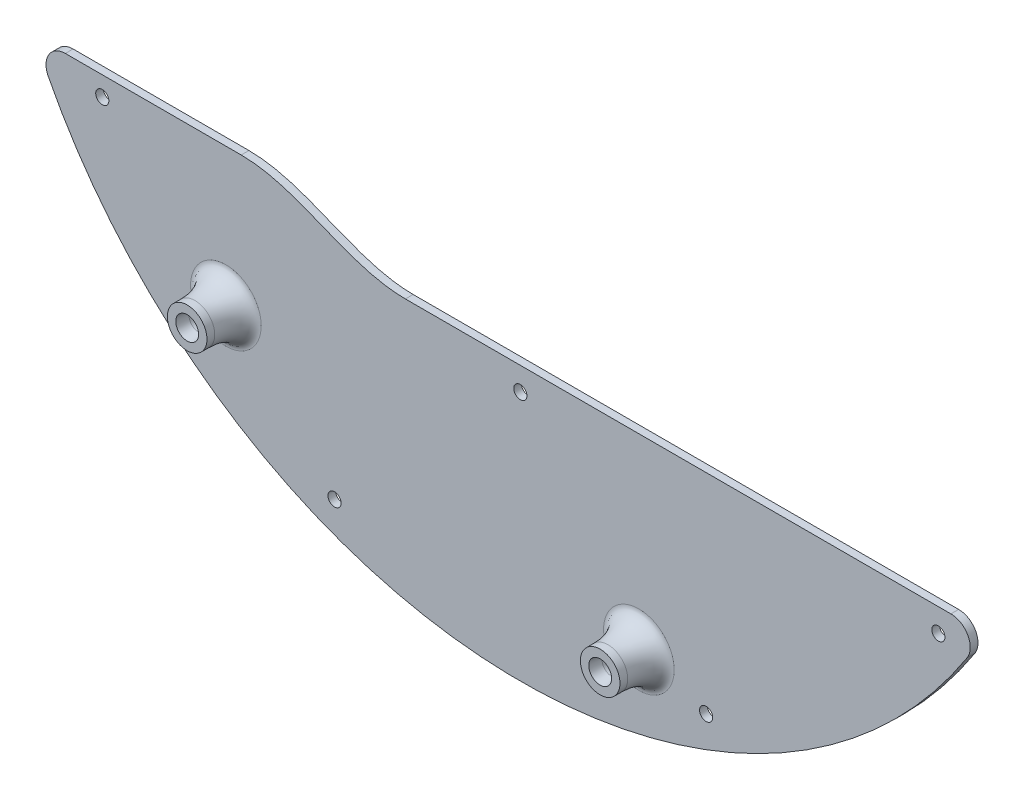
SolidWorks part; units mm, degrees
ref_plane "Ground plane" through (0, 0, 0) normal (0, 0, 1) x (1, 0, 0)
ref_plane "Medial plane" through (0, 0, 0) normal (0, 1, 0) x (1, 0, 0)
ref_plane "Frontal plane" through (0, 0, 0) normal (1, 0, 0) x (0, 0, -1)
sketch "Hole Pattern" plane through (0, 0, 0) normal (0, 0, 1) x (1, 0, 0)
  line L0 (0, 0) -> (0, 132) construction
  circle A92 centre (-108, 60) radius 1.5437
  circle A93 centre (-96, 60) radius 1.5437
  circle A94 centre (-84, 60) radius 1.5437
  circle A95 centre (-72, 60) radius 1.5437
  circle A96 centre (-60, 60) radius 1.5437
  circle A97 centre (-48, 60) radius 1.5437
  circle A98 centre (-36, 60) radius 1.5437
  circle A99 centre (-24, 60) radius 1.5437
  circle A100 centre (-12, 60) radius 1.5437
  circle A101 centre (0, 60) radius 1.5437
  circle A102 centre (12, 60) radius 1.5437
  circle A103 centre (24, 60) radius 1.5437
  circle A104 centre (36, 60) radius 1.5437
  circle A105 centre (48, 60) radius 1.5437
  circle A106 centre (96, 60) radius 1.5437
  circle A107 centre (108, 60) radius 1.5437
  circle A108 centre (-96, 72) radius 1.5437
  circle A109 centre (-84, 72) radius 1.5437
  circle A110 centre (-72, 72) radius 1.5437
  circle A111 centre (-60, 72) radius 1.5437
  circle A112 centre (-48, 72) radius 1.5437
  circle A113 centre (-36, 72) radius 1.5437
  circle A114 centre (-24, 72) radius 1.5437
  circle A115 centre (-12, 72) radius 1.5437
  circle A116 centre (0, 72) radius 1.5437
  circle A117 centre (12, 72) radius 1.5437
  circle A118 centre (24, 72) radius 1.5437
  circle A119 centre (36, 72) radius 1.5437
  circle A120 centre (48, 72) radius 1.5437
  circle A121 centre (60, 72) radius 1.5437
  circle A122 centre (72, 72) radius 1.5437
  circle A123 centre (84, 72) radius 1.5437
  circle A124 centre (96, 72) radius 1.5437
  circle A125 centre (108, 72) radius 1.5437
  circle A126 centre (-96, 84) radius 1.5437
  circle A127 centre (-84, 84) radius 1.5437
  circle A128 centre (-72, 84) radius 1.5437
  circle A129 centre (-60, 84) radius 1.5437
  circle A130 centre (-48, 84) radius 1.5437
  circle A131 centre (-36, 84) radius 1.5437
  circle A132 centre (-24, 84) radius 1.5437
  circle A133 centre (-12, 84) radius 1.5437
  circle A134 centre (0, 84) radius 1.5437
  circle A135 centre (12, 84) radius 1.5437
  circle A136 centre (24, 84) radius 1.5437
  circle A137 centre (36, 84) radius 1.5437
  circle A138 centre (48, 84) radius 1.5437
  circle A139 centre (60, 84) radius 1.5437
  circle A140 centre (72, 84) radius 1.5437
  circle A141 centre (84, 84) radius 1.5437
  circle A142 centre (96, 84) radius 1.5437
  circle A143 centre (-84, 96) radius 1.5437
  circle A144 centre (-72, 96) radius 1.5437
  circle A145 centre (-60, 96) radius 1.5437
  circle A146 centre (-48, 96) radius 1.5437
  circle A147 centre (-36, 96) radius 1.5437
  circle A148 centre (-24, 96) radius 1.5437
  circle A149 centre (-12, 96) radius 1.5437
  circle A150 centre (0, 96) radius 1.5437
  circle A151 centre (12, 96) radius 1.5437
  circle A152 centre (24, 96) radius 1.5437
  circle A153 centre (36, 96) radius 1.5437
  circle A154 centre (48, 96) radius 1.5437
  circle A155 centre (60, 96) radius 1.5437
  circle A156 centre (72, 96) radius 1.5437
  circle A157 centre (84, 96) radius 1.5437
  circle A158 centre (-72, 108) radius 1.5437
  circle A159 centre (-60, 108) radius 1.5437
  circle A160 centre (-48, 108) radius 1.5437
  circle A161 centre (-36, 108) radius 1.5437
  circle A162 centre (-24, 108) radius 1.5437
  circle A163 centre (-12, 108) radius 1.5437
  circle A164 centre (0, 108) radius 1.5437
  circle A165 centre (12, 108) radius 1.5437
  circle A166 centre (24, 108) radius 1.5437
  circle A167 centre (36, 108) radius 1.5437
  circle A168 centre (48, 108) radius 1.5437
  circle A169 centre (60, 108) radius 1.5437
  circle A170 centre (72, 108) radius 1.5437
  circle A171 centre (-48, 120) radius 1.5437
  circle A172 centre (-36, 120) radius 1.5437
  circle A173 centre (-24, 120) radius 1.5437
  circle A174 centre (-12, 120) radius 1.5437
  circle A175 centre (0, 120) radius 1.5437
  circle A176 centre (12, 120) radius 1.5437
  circle A177 centre (24, 120) radius 1.5437
  circle A178 centre (36, 120) radius 1.5437
  circle A179 centre (48, 120) radius 1.5437
  circle A180 centre (-12, 132) radius 1.5437
  circle A181 centre (0, 132) radius 1.5437
  circle A182 centre (12, 132) radius 1.5437
  circle A183 centre (-108, 72) radius 1.5437
sketch "Base Outline" plane through (0, 0, 0) normal (0, 0, 1) x (1, 0, 0)
  line L3 (-125.4751, 55) -> (-40.5641, 55)
  line L4 (-40.5641, 55) -> (-40.5641, 66)
  line L5 (120.0542, 66) -> (-40.5641, 66)
  circle A1 centre (0, 0) radius 137 construction
  arc A2 (120.0542, 66) -> (-125.4751, 55) centre (0, 0) ccw
  dimension "D1" = 274
  dimension "D2" = 11
  dimension "D3" = 6
sketch "TTB4 Standard Top Plate Outline" plane through (0, 0, 0) normal (0, 0, 1) x (1, 0, 0)
  line L2 (115, -70.7107) -> (115, 70.7107)
  circle A0 centre (-76.0694, -90.6262) radius 2.25
  arc A2 (115, 70.7107) -> (115, -70.7107) centre (0, 0) ccw
  circle A3 centre (30.6294, -114.2808) radius 2.25
  circle A4 centre (30.6294, 114.3106) radius 2.25
  circle A5 centre (-76.0694, 90.656) radius 2.25
sketch "Sketch2" plane through (0, 0, 0) normal (0, 0, 1) x (1, 0, 0)
  line L0 (-125.4751, 55) -> (-40.5641, 55) construction
  line L1 (120.0542, 66) -> (-40.5641, 66) construction
  line L2 (111.2396, 66) -> (-29.6958, 66)
  line L3 (-72.1027, 55) -> (-117.5419, 55)
  arc A0 (-121.9866, 62.2901) -> (115.4441, 73.7059) centre (0.0258, -0.575) cw
  circle A1 centre (0, 0) radius 137 construction
  arc A2 (-121.9866, 62.2901) -> (-117.5419, 55) centre (-117.5419, 60) ccw
  arc A3 (115.4441, 73.7059) -> (111.2396, 66) centre (111.2396, 71) cw
  spline S0 degree 3 poles (-72.1027, 55) (-57.0449, 55) (-44.8946, 66) (-29.6958, 66) knots 0 0 0 0 1 1 1 1
  point P21 (-125.4751, 55)
  point P24 (120.0542, 66)
  dimension "D1" = 5
extrude "Plate" add sketch "Sketch2" along normal blind 2
hole_wizard "Mounting Holes (M3)" positions "Sketch4" profile "Sketch5" hole size "M3" standard "ANSI Metric" end condition through all
sketch "Sketch4" plane through (0, 0, 2) normal (0, 0, 1) x (1, 0, 0)
  point P0 (108, 72)
  point P3 (48, 120)
  point P6 (-48, 120)
  point P9 (-108, 60)
  point P25 (0, 72)
sketch "Sketch5" plane through (108, 72, 2) normal (1, 0, 0) x (0, -1, 0)
  line L0 (0, 0) -> (0, 2)
  line L1 (0, 2) -> (1.7, 2)
  line L2 (1.7, 2) -> (1.7, 0)
  line L5 (1.7, 0) -> (0, 0)
  line L11 (0, -6.35) -> (0, 107.95) construction
  dimension "Thru Hole Dia." = 3.4
  dimension "Thru Hole Depth" = 2
sketch "Sketch7" plane through (0, 0, 2) normal (0, 0, 1) x (1, 0, 0)
  line L1 (-71.4506, 90.656) -> (-73.76, 94.656) construction
  line L2 (-73.76, 94.656) -> (-78.3789, 94.656) construction
  line L3 (-78.3789, 94.656) -> (-80.6883, 90.656) construction
  line L4 (-80.6883, 90.656) -> (-78.3789, 86.656) construction
  line L5 (-78.3789, 86.656) -> (-73.76, 86.656) construction
  line L6 (-73.76, 86.656) -> (-71.4506, 90.656) construction
  circle A0 centre (-76.0694, 90.656) radius 4 construction
  circle A1 centre (-76.0694, 90.656) radius 5.1188
  circle A2 centre (-76.0694, 90.656) radius 4.6188 construction
  circle A3 centre (30.6294, 114.3106) radius 5.1188
  dimension "D1" = 8
  dimension "D2" = 0.5
extrude "Boss-Extrude2" add sketch "Sketch7" along normal blind 10
hole_wizard "#8 (0.199) Diameter Hole1" positions "Sketch8" profile "Sketch9" hole size "#8" standard "ANSI Inch"
sketch "Sketch8" plane through (0, 0, 12) normal (0, 0, 1) x (1, 0, 0)
  point P0 (-76.0694, 90.656)
  point P3 (30.6294, 114.3106)
sketch "Sketch9" plane through (-76.0694, 90.656, 12) normal (1, 0, 0) x (0, -1, 0)
  line L0 (0, 0) -> (0, 11.5176)
  line L1 (0, 11.5176) -> (2.5273, 9.999)
  line L2 (2.5273, 9.999) -> (2.5273, 0)
  line L5 (2.5273, 0) -> (0, 0)
  line L10 (0, 11.5176) -> (-2.5273, 9.999) construction
  line L11 (0, -6.35) -> (0, 107.95) construction
  dimension "Hole Dia." = 5.0546
  dimension "Hole Depth" = 9.999
  dimension "Drill Angle" = 118
fillet "Fillet1" radius 8 2 edges at (25.5106, 114.3106, 2) (-81.1883, 90.656, 2) second distance 4 first distance on face at (35.7482, 114.3106, 12) first distance on face at (-70.9506, 90.656, 12)
chamfer "Chamfer2" distance 3 angle 8 2 edges at (33.1567, 114.3106, 12) (-73.5421, 90.656, 12) first distance on face at (33.1567, 114.3106, 2) first distance on face at (-73.5421, 90.656, 2)
mirror "Mirror2" about plane through (0, 0, 0) normal (0, 1, 0) of bodies 104
delete or keep bodies "Body-Delete/Keep 1" type delete bodies bodies 104
